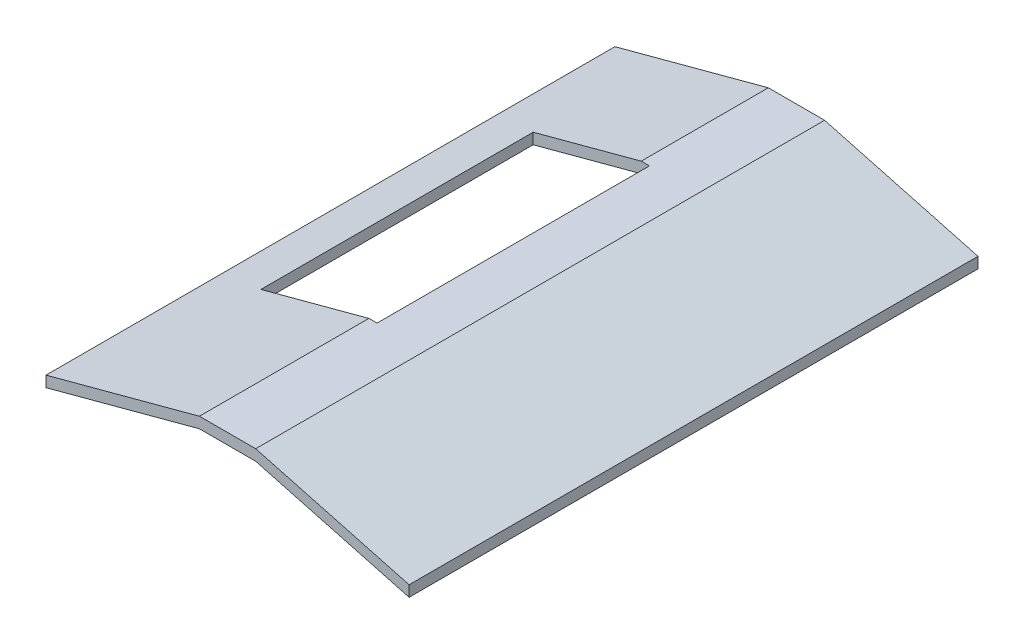
SolidWorks part; units mm, degrees
ref_plane "Ebene vorne" through (0, 0, 0) normal (0, 0, 1) x (1, 0, 0)
ref_plane "Ebene oben" through (0, 0, 0) normal (0, 1, 0) x (1, 0, 0)
ref_plane "Ebene rechts" through (0, 0, 0) normal (1, 0, 0) x (0, 0, -1)
sketch "Skizze1" plane through (0, 0, 0) normal (0, 0, 1) x (1, 0, 0)
  line L0 (650.3605, 174.2211) -> (650.3605, 144.2211)
  line L5 (650.3605, 144.2211) -> (227.8605, 257.4296)
  line L6 (227.8605, 257.4296) -> (72.8605, 257.4296)
  line L7 (72.8605, 257.4296) -> (-349.6395, 144.2211)
  line L8 (-349.6395, 144.2211) -> (-349.6395, 174.2211)
  line L9 (-349.6395, 174.2211) -> (72.8605, 287.4296)
  line L10 (72.8605, 287.4296) -> (227.8605, 287.4296)
  line L11 (227.8605, 287.4296) -> (650.3605, 174.2211)
  point P0 (0, 0)
  point P7 (650.3605, 159.2211)
  dimension "D1" = 105
  dimension "D2" = 1000
  dimension "D3" = 155
  dimension "D4" = 30
extrude "Aufsatz-Linear austragen1" add sketch "Skizze1" along normal blind 1566.7
sketch "Skizze2" plane through (0, 287.4296, 0) normal (0, 1, 0) x (1, 0, 0)
  line L0 (227.8605, 0) -> (72.8605, 0) construction
  line L1 (95.3605, -350) -> (-224.6395, -350)
  line L2 (95.3605, -350) -> (95.3605, -1100)
  line L3 (95.3605, -1100) -> (-224.6395, -1100)
  line L4 (-224.6395, -350) -> (-224.6395, -1100)
  line L5 (150.3605, -1373.6948) -> (150.3605, -430.1532) construction
  dimension "D1" = 350
  dimension "D2" = 55
  dimension "D3" = 750
  dimension "D4" = 320
extrude "Schnitt-Linear austragen1" cut sketch "Skizze2" against normal up to next
